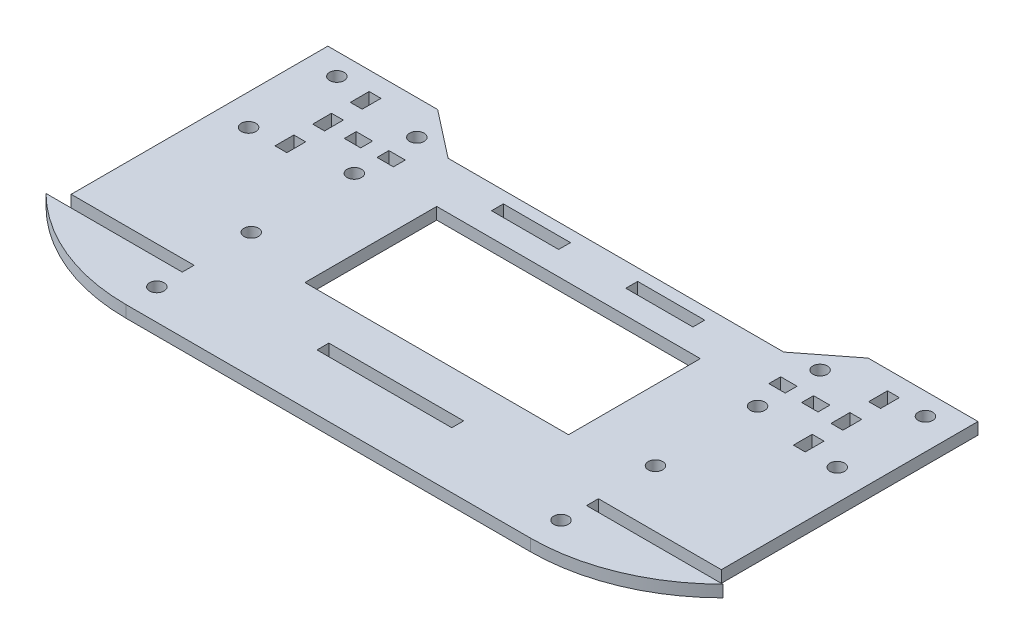
SolidWorks part; units mm, degrees
ref_plane "Ön Düzlem" through (0, 0, 0) normal (0, 0, 1) x (1, 0, 0)
ref_plane "Üst Düzlem" through (0, 0, 0) normal (0, 1, 0) x (1, 0, 0)
ref_plane "Sağ Düzlem" through (0, 0, 0) normal (1, 0, 0) x (0, 0, -1)
sketch "Sketch1" plane through (0, 0, 0) normal (0, 1, 0) x (1, 0, 0)
  line L1 (-46, 0) -> (46, 0)
  line L19 (-73.9952, 35.5) -> (-73.9952, 15.5)
  line L21 (73.9952, 35.5) -> (73.9952, 15.5)
  line L22 (-15.34, 15.5) -> (-15.34, 12.8)
  line L23 (-46.0152, 15.5) -> (-46.0152, 12.8)
  line L24 (-15.34, 12.8) -> (15.34, 12.8)
  line L25 (15.34, 12.8) -> (15.34, 15.5)
  line L26 (15.34, 15.5) -> (-15.34, 15.5)
  line L29 (46.0152, 15.5) -> (46.0152, 12.8)
  line L31 (46.0152, 15.5) -> (73.9952, 15.5)
  line L32 (77.0252, 12.8) -> (46.0152, 12.8)
  line L33 (-46.0152, 15.5) -> (-73.9952, 15.5)
  line L34 (-46.0152, 12.8) -> (-77.0252, 12.8)
  line L39 (-38.2, 65.5) -> (38.2, 65.5)
  line L45 (-22.92, 62.8) -> (-7.64, 62.8)
  line L47 (7.64, 62.8) -> (22.92, 62.8)
  line L48 (38.2, 65.5) -> (48.9952, 73.92)
  line L49 (22.92, 60.1) -> (7.64, 60.1)
  line L51 (-7.64, 60.1) -> (-22.92, 60.1)
  line L53 (-22.92, 62.8) -> (-22.92, 60.1)
  line L54 (-7.64, 62.8) -> (-7.64, 60.1)
  line L55 (7.64, 62.8) -> (7.64, 60.1)
  line L56 (22.92, 62.8) -> (22.92, 60.1)
  line L81 (73.9952, 35.5) -> (73.9952, 43.92)
  line L82 (-73.9952, 35.5) -> (-73.9952, 43.92)
  line L83 (68.9952, 73.92) -> (73.9952, 73.92)
  line L84 (60.3452, 56.8171) -> (57.6452, 56.8171)
  line L85 (57.6452, 56.8171) -> (57.6452, 61.1028)
  line L86 (42.7252, 57.578) -> (42.7252, 60.278)
  line L87 (68.9952, 73.92) -> (48.9952, 73.92)
  line L88 (42.7252, 57.578) -> (46.4552, 57.578)
  line L89 (57.6452, 48.2457) -> (57.6452, 52.5314)
  line L90 (57.6452, 52.5314) -> (60.3452, 52.5314)
  line L91 (60.3452, 65.3885) -> (57.6452, 65.3885)
  line L93 (46.4552, 57.578) -> (46.4552, 60.278)
  line L94 (68.9952, 73.92) -> (48.9952, 43.92) construction
  line L95 (50.1852, 60.294) -> (53.9152, 60.294)
  line L96 (60.3452, 56.8171) -> (60.3452, 61.1028)
  line L97 (57.6452, 69.6743) -> (60.3452, 69.6743)
  line L99 (57.6452, 61.1028) -> (60.3452, 61.1028)
  line L103 (57.6452, 65.3885) -> (57.6452, 69.6743)
  line L104 (50.1852, 57.594) -> (53.9152, 57.594)
  line L105 (68.9952, 43.92) -> (48.9952, 73.92) construction
  line L106 (57.6452, 48.2457) -> (60.3452, 48.2457)
  line L107 (50.1852, 60.294) -> (50.1852, 57.594)
  line L108 (60.3452, 48.2457) -> (60.3452, 52.5314)
  line L109 (42.7252, 60.278) -> (46.4552, 60.278)
  line L110 (60.3452, 65.3885) -> (60.3452, 69.6743)
  line L111 (73.9952, 73.92) -> (73.9952, 43.92)
  line L112 (53.9152, 60.294) -> (53.9152, 57.594)
  line L115 (-53.9152, 60.294) -> (-53.9152, 57.594)
  line L116 (-50.1852, 60.294) -> (-50.1852, 57.594)
  line L117 (-46.4552, 57.578) -> (-46.4552, 60.278)
  line L118 (-42.7252, 57.578) -> (-42.7252, 60.278)
  line L119 (-50.1852, 57.594) -> (-53.9152, 57.594)
  line L120 (-42.7252, 57.578) -> (-46.4552, 57.578)
  line L121 (-50.1852, 60.294) -> (-53.9152, 60.294)
  line L123 (-42.7252, 60.278) -> (-46.4552, 60.278)
  line L124 (-57.6452, 69.6743) -> (-60.3452, 69.6743)
  line L125 (-60.3452, 65.3885) -> (-57.6452, 65.3885)
  line L126 (-57.6452, 61.1028) -> (-60.3452, 61.1028)
  line L127 (-60.3452, 56.8171) -> (-57.6452, 56.8171)
  line L128 (-57.6452, 52.5314) -> (-60.3452, 52.5314)
  line L129 (-57.6452, 48.2457) -> (-60.3452, 48.2457)
  line L130 (-73.9952, 73.92) -> (-73.9952, 43.92)
  line L131 (-57.6452, 65.3885) -> (-57.6452, 69.6743)
  line L132 (-57.6452, 56.8171) -> (-57.6452, 61.1028)
  line L133 (-68.9952, 73.92) -> (-73.9952, 73.92)
  line L134 (-57.6452, 48.2457) -> (-57.6452, 52.5314)
  line L135 (-60.3452, 65.3885) -> (-60.3452, 69.6743)
  line L136 (-60.3452, 56.8171) -> (-60.3452, 61.1028)
  line L139 (-60.3452, 48.2457) -> (-60.3452, 52.5314)
  line L140 (-68.9952, 73.92) -> (-48.9952, 73.92)
  line L142 (-38.2, 65.5) -> (-48.9952, 73.92)
  line L144 (30, 24.71) -> (-30, 24.71)
  line L145 (30, 24.71) -> (30, 54.71)
  line L146 (30, 54.71) -> (-30, 54.71)
  line L147 (-30, 24.71) -> (-30, 54.71)
  arc A0 (-77.0252, 12.8) -> (-46, 0) centre (-46, 44) ccw
  arc A1 (46, 0) -> (77.0252, 12.8) centre (46, 44) ccw
  circle A2 centre (46, 28.5) radius 1.65
  circle A3 centre (46, 7) radius 1.65
  circle A4 centre (-46, 7) radius 1.65
  circle A5 centre (-46, 28.5) radius 1.65
  circle A10 centre (66.9952, 68.96) radius 1.65
  circle A11 centre (66.9952, 48.88) radius 1.65
  circle A12 centre (45.8923, 66.0768) radius 1.65
  circle A13 centre (45.8923, 51.8431) radius 1.65
  circle A14 centre (-66.9952, 48.88) radius 1.65
  circle A15 centre (-45.8923, 66.0768) radius 1.65
  circle A16 centre (-66.9952, 68.96) radius 1.65
  circle A17 centre (-45.8923, 51.8431) radius 1.65
  point P76 (58.9952, 58.92)
  point P181 (-58.9952, 58.92)
  dimension "D1" = 60
  dimension "D2" = 30
  dimension "D3" = 30
  dimension "D4" = 20
extrude "Boss-Extrude1" add sketch "Sketch1" along normal blind 2.7
